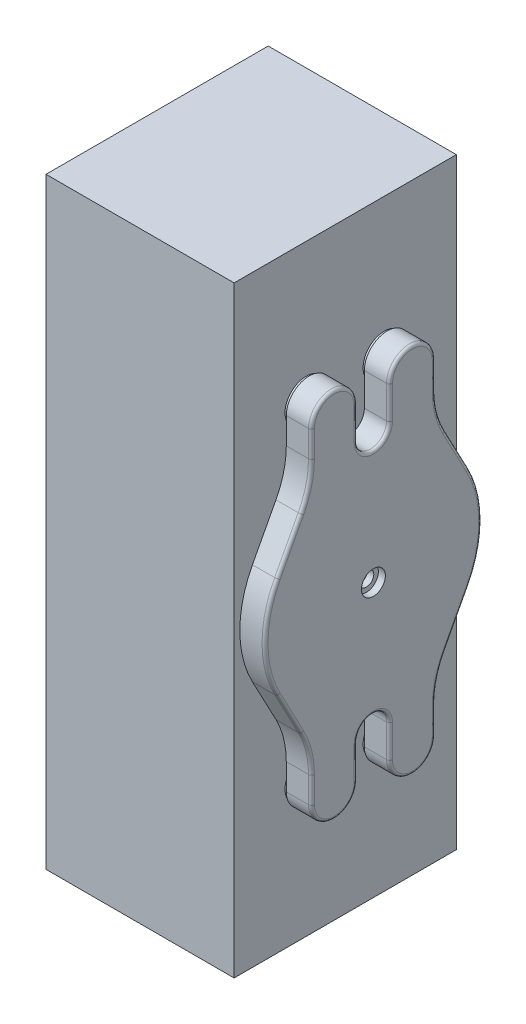
SolidWorks part; units mm, degrees
other "Markup1"
sketch "Sketch9" plane through (-25.745, 62.7203, -36.576) normal (-0.5706, 0.1284, -0.8112) x (-0.8147, 0.0363, 0.5788)
ref_plane "Front Plane" through (0, 0, 0) normal (0, 0, 1) x (1, 0, 0)
ref_plane "Top Plane" through (0, 0, 0) normal (0, 1, 0) x (1, 0, 0)
ref_plane "Right Plane" through (0, 0, 0) normal (1, 0, 0) x (0, 0, -1)
sketch "Sketch1" plane through (0, 0, 0) normal (0, 0, 1) x (1, 0, 0)
  line L0 (8.255, 0) -> (-8.255, 0) construction
  line L1 (26.255, 0) -> (-26.255, 0) construction
  line L2 (8.255, 0) -> (8.255, 18.25)
  line L3 (8.255, 18.25) -> (26.255, 18.25)
  line L4 (26.255, 18.25) -> (26.255, 0)
  line L5 (8.255, 0) -> (26.255, 0)
  point P4 (0, 0)
  point P8 (0, 0)
  dimension "D1" = 16.51
  dimension "D2" = 18
  dimension "D3" = 18.25
revolve "Revolve1" add sketch "Sketch1" angle 360 about L5
sketch "Sketch2" plane through (8.255, 0, 0) normal (-1, 0, 0) x (0, 0, 1)
  circle A0 centre (0, 0) radius 3.7145
  dimension "D1" = 7.429
extrude "Cut-Extrude1" cut sketch "Sketch2" against normal blind 8.5725
sketch "Sketch3" plane through (26.255, 0, 0) normal (1, 0, 0) x (0, 0, -1)
  line L0 (-20.8953, -55) -> (-20.8953, -46.1532)
  line L1 (13.175, -55) -> (-13.175, -55) construction
  line L2 (13.175, -55) -> (13.175, 55) construction
  line L3 (13.175, 55) -> (-13.175, 55) construction
  line L4 (-13.175, -55) -> (-13.175, 55) construction
  line L5 (13.175, -55) -> (-13.175, 55) construction
  line L6 (13.175, 55) -> (-13.175, -55) construction
  line L7 (-24.3823, -32.1152) -> (-32.3245, -17.1152)
  line L9 (-5.4548, -55) -> (-5.4548, -44)
  line L11 (5.4547, -44) -> (5.4547, -55)
  line L12 (20.8953, -55) -> (20.8953, -46.1532)
  line L13 (24.3823, -32.1152) -> (32.3245, -17.1152)
  line L14 (9.9, 0) -> (-9.9, 0) construction
  line L15 (13.175, -55) -> (-13.175, 55) construction
  line L16 (13.175, 55) -> (-13.175, -55) construction
  line L17 (13.175, 55) -> (-13.175, 55) construction
  line L18 (24.3823, 32.1152) -> (32.3245, 17.1152)
  line L19 (20.8953, 55) -> (20.8953, 46.1532)
  line L20 (5.4547, 44) -> (5.4547, 55)
  line L21 (-5.4548, 55) -> (-5.4548, 44)
  line L22 (-24.3823, 32.1152) -> (-32.3245, 17.1152)
  line L23 (-20.8953, 55) -> (-20.8953, 46.1532)
  arc A15 (32.3245, -17.1152) -> (32.3245, 17.1152) centre (0, 0) ccw
  arc A16 (-5.4548, 55) -> (-20.8953, 55) centre (-13.175, 55) ccw
  arc A17 (-20.8953, -55) -> (-5.4548, -55) centre (-13.175, -55) ccw
  arc A18 (5.4547, -55) -> (20.8953, -55) centre (13.175, -55) ccw
  arc A19 (20.8953, 55) -> (5.4547, 55) centre (13.175, 55) ccw
  arc A20 (-5.4548, -44) -> (5.4547, -44) centre (0, -44) cw
  arc A21 (20.8953, -46.1532) -> (24.3823, -32.1152) centre (50.8953, -46.1532) cw
  arc A22 (-20.8953, -46.1532) -> (-24.3823, -32.1152) centre (-50.8953, -46.1532) ccw
  arc A23 (-20.8953, 46.1532) -> (-24.3823, 32.1152) centre (-50.8953, 46.1532) cw
  arc A24 (20.8953, 46.1532) -> (24.3823, 32.1152) centre (50.8953, 46.1532) ccw
  arc A25 (-5.4548, 44) -> (5.4547, 44) centre (0, 44) ccw
  arc A26 (5.4547, 55) -> (20.8953, 55) centre (13.175, 55) cw
  arc A27 (-20.8953, 55) -> (-5.4548, 55) centre (-13.175, 55) cw
  arc A29 (-32.3245, 17.1152) -> (-32.3245, -17.1152) centre (0, 0) ccw
  circle M2 centre (0, 0) radius 18.25
  dimension "D3" = 15.4405
  dimension "D5" = 7.7203
  dimension "D4" = 30
  dimension "D7" = 15
  dimension "D9" = 110
  dimension "D1" = 73.152
  dimension "D6" = 15
  dimension "D2" = 26.35
  dimension "D8" = 11
extrude "Boss-Extrude1" add sketch "Sketch3" along normal blind 8.5 separate body contours L22 A29 L7 A22 L0 A17 L9 A20 L11 A18 L12 A21 L13 A15 L18 A24 L19 A19 L20 A25 L21 A16 L23 A23 M2 | M2 region at (26.255, -50.5766, 19.4431) region at (26.255, 0, 0)
sketch "Sketch4" plane through (26.255, 0, 0) normal (-1, 0, 0) x (0, 0, 1)
  line L0 (-20.8953, 55) -> (-5.4547, 55) construction
  line L1 (13.175, -55) -> (-13.175, -55) construction
  line L2 (13.175, -55) -> (13.175, 55) construction
  line L3 (13.175, 55) -> (-13.175, 55) construction
  line L4 (-13.175, -55) -> (-13.175, 55) construction
  line L5 (13.175, -55) -> (-13.175, 55) construction
  line L6 (13.175, 55) -> (-13.175, -55) construction
  circle A0 centre (-13.175, 55) radius 4.75
  circle A1 centre (13.175, -55) radius 4.75
  circle A2 centre (13.175, 55) radius 4.75
  circle A3 centre (-13.175, -55) radius 4.75
  arc A4 (-5.4547, 55) -> (-20.8953, 55) centre (-13.175, 55) ccw construction
  circle A5 centre (-13.175, 55) radius 6.4
  circle A6 centre (13.175, 55) radius 6.4
  circle A7 centre (13.175, -55) radius 6.4
  circle A8 centre (-13.175, -55) radius 6.4
  point P6 (0, 0)
  dimension "D1" = 9.5
  dimension "D2" = 12.8
extrude "Boss-Extrude2" add sketch "Sketch4" along normal blind 52
sketch "Sketch5" plane through (8.255, 0, 0) normal (-1, 0, 0) x (0, 0, 1)
  circle A0 centre (0, 0) radius 18.25
  dimension "D1" = 36.5
fillet "Fillet1" radius 1 24 edges at (34.755, 38.9209, 21.7801) (34.755, 50.5766, 20.8953) (34.755, 62.7203, 13.175) (34.755, 49.5, 5.4548) (34.755, 38.5453, 0) (34.755, 49.5, -5.4547) (34.755, 62.7203, -13.175) (34.755, 50.5766, -20.8953) (34.755, 38.9209, -21.7801) (34.755, 24.6152, -28.3534) (34.755, 0, -36.576) (34.755, -24.6152, -28.3534) (34.755, -38.9209, -21.7801) (34.755, -50.5766, -20.8953) (34.755, -62.7202, -13.175) (34.755, -49.5, -5.4547) (34.755, -38.5452, 0) (34.755, -49.5, 5.4548) (34.755, -62.7202, 13.175) (34.755, -50.5766, 20.8953) (34.755, -38.9209, 21.7801) (34.755, -24.6152, 28.3534) (34.755, 0, 36.576) (34.755, 24.6152, 28.3534)
sketch "Sketch6" plane through (8.255, 0, 0) normal (-1, 0, 0) x (0, 0, 1)
  circle A0 centre (0, 0) radius 18.25 construction
  circle A1 centre (0, 0) radius 18.25
extrude "Cut-Extrude2" cut sketch "Sketch6" against normal blind 22
sketch "Sketch7" plane through (0, 0, 0) normal (0, 0, 1) x (1, 0, 0)
  line L0 (0, 0) -> (28.255, 0) construction
  line L2 (28.255, 18.25) -> (28.255, -18.25) construction
  line L3 (30.255, 18.25) -> (26.255, 18.25) construction
  line L4 (26.255, -18.25) -> (30.255, -18.25) construction
  circle A0 centre (28.255, 0) radius 1.6
  circle A1 centre (28.255, 0) radius 2.875 construction
  dimension "D1" = 3.2
  dimension "D2" = 5.75
extrude "Cut-Extrude3" [suppressed] cut sketch "Sketch7" against normal through all and the other way through all
ref_plane "Plane1" through (0, 0, 38) normal (0, 0, 1) x (1, 0, 0)
sketch "Sketch8" [suppressed] plane through (0, 0, 38) normal (0, 0, 1) x (1, 0, 0)
  circle A0 centre (31.005, 0) radius 2.875
  dimension "D1" = 5.75
extrude "Cut-Extrude4" [suppressed] cut sketch "Sketch8" against normal blind 16
mirror "Mirror1" [suppressed] about plane through (0, 0, 0) normal (0, 0, 1)
ref_plane "Plane2" through (25.255, 0, 0) normal (-1, 0, 0) x (0, 0, 1)
sketch "Sketch10" plane through (25.255, 0, 0) normal (-1, 0, 0) x (0, 0, 1)
  line L1 (37.5, -101.6) -> (-37.5, -101.6)
  line L2 (37.5, -101.6) -> (37.5, 101.6)
  line L3 (37.5, 101.6) -> (-37.5, 101.6)
  line L4 (-37.5, -101.6) -> (-37.5, 101.6)
  line L5 (37.5, -101.6) -> (-37.5, 101.6) construction
  line L6 (37.5, 101.6) -> (-37.5, -101.6) construction
  circle A0 centre (-13.175, 55) radius 7.15
  circle A1 centre (13.175, 55) radius 7.15
  circle A2 centre (-13.175, -55) radius 7.15
  circle A3 centre (13.175, -55) radius 7.15
  circle A4 centre (-13.175, 55) radius 6.4 construction
  circle A5 centre (0, 0) radius 18.75
  circle A6 centre (0, 0) radius 18.25 construction
  point P0 (0, 0)
  dimension "D3" = 0.75
  dimension "D4" = 0.5
  dimension "D1" = 75
  dimension "D2" = 203.2
extrude "Boss-Extrude3" add sketch "Sketch10" along normal blind 63.5 separate body
sketch "Sketch11" plane through (0, -101.6, 0) normal (0, -1, 0) x (1, 0, 0)
  line L0 (-38.245, -37.5) -> (-38.245, 37.5) construction
  line L1 (8.505, -27.5) -> (-21.495, -27.5) construction
  line L2 (8.505, -27.5) -> (8.505, 27.5) construction
  line L3 (8.505, 27.5) -> (-21.495, 27.5) construction
  line L4 (-21.495, -27.5) -> (-21.495, 27.5) construction
  line L5 (8.505, -27.5) -> (-21.495, 27.5) construction
  line L6 (8.505, 27.5) -> (-21.495, -27.5) construction
  line L7 (-38.245, 37.5) -> (25.255, 37.5) construction
  circle A0 centre (-21.495, 27.5) radius 2.25
  circle A1 centre (8.505, 27.5) radius 2.25
  circle A2 centre (-21.495, -27.5) radius 2.25
  circle A3 centre (8.505, -27.5) radius 2.25
  circle A4 centre (-6.495, 0) radius 17.5
  dimension "D3" = 4.5
  dimension "D4" = 35
  dimension "D1" = 30
  dimension "D2" = 55
  dimension "D5" = 31.75
  dimension "D6" = 37.5
extrude "Cut-Extrude5" cut sketch "Sketch11" against normal blind 6 contours A0 | A1 | A2 | A3 region at (-21.495, -101.6, 27.5) region at (8.505, -101.6, 27.5) region at (-21.495, -101.6, -27.5) region at (8.505, -101.6, -27.5)
sketch "Sketch12" plane through (34.755, 0, 0) normal (1, 0, 0) x (0, 0, -1)
  circle A0 centre (0, 0) radius 4.05
  circle A1 centre (0, 0) radius 2.5
  dimension "D1" = 8.1
  dimension "D2" = 5
extrude "Cut-Extrude6" cut sketch "Sketch12" against normal blind 2.36 contours A1 | A0 A1 region at (34.755, 0, 3.9354) region at (34.755, 0, 0)
extrude "Cut-Extrude7" cut sketch "Sketch12<3>" against normal up to surface (4.5 mm away) contours A1 region at (34.755, 0, 0) up to face at (30.255, -18.25, 0)
sketch "Sketch12<3>" plane through (34.755, 0, 0) normal (1, 0, 0) x (0, 0, -1) same geometry as "Sketch12"
